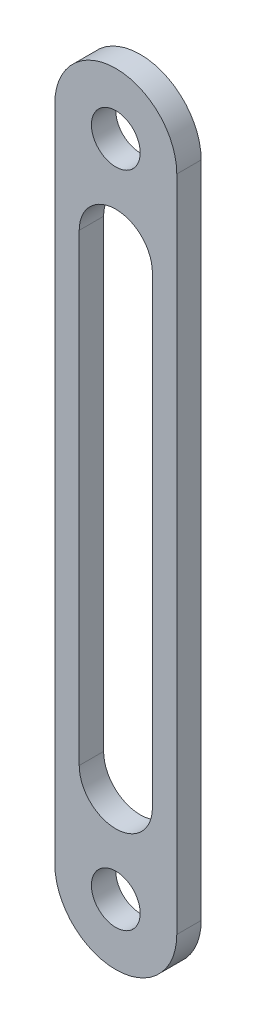
SolidWorks part; units mm, degrees
material "PLA"
ref_plane "Alzado" through (0, 0, 0) normal (0, 0, 1) x (1, 0, 0)
ref_plane "Planta" through (0, 0, 0) normal (0, 1, 0) x (1, 0, 0)
ref_plane "Vista lateral" through (0, 0, 0) normal (1, 0, 0) x (0, 0, -1)
sketch "Croquis1" plane through (0, 0, 0) normal (0, 0, 1) x (1, 0, 0)
  line L0 (0, 54) -> (0, -54) construction
  line L1 (10, 54) -> (10, -54)
  line L2 (-10, 54) -> (-10, -54)
  line L3 (0, 38) -> (0, -38) construction
  line L4 (6, 38) -> (6, -38)
  line L5 (-6, 38) -> (-6, -38)
  arc A0 (10, 54) -> (-10, 54) centre (0, 54) ccw
  arc A1 (-10, -54) -> (10, -54) centre (0, -54) ccw
  circle A2 centre (0, 54) radius 4
  circle A3 centre (0, -54) radius 4
  arc A4 (6, 38) -> (-6, 38) centre (0, 38) ccw
  arc A5 (-6, -38) -> (6, -38) centre (0, -38) ccw
  point P2 (0, 0)
  point P14 (0, 0)
  dimension "D1" = 8
  dimension "D2" = 20
  dimension "D3" = 108
  dimension "D4" = 4
  dimension "D5" = 16
extrude "Saliente-Extruir1" add sketch "Croquis1" along normal blind 4
